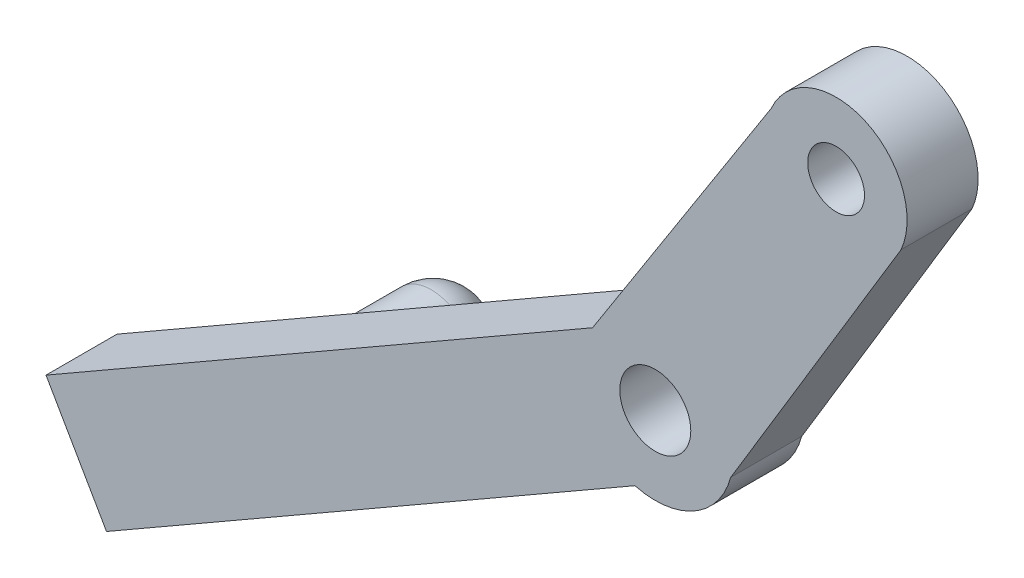
SolidWorks part; units mm, degrees
ref_plane "Front Plane" through (0, 0, 0) normal (0, 0, 1) x (1, 0, 0)
ref_plane "Top Plane" through (0, 0, 0) normal (0, 1, 0) x (1, 0, 0)
ref_plane "Right Plane" through (0, 0, 0) normal (1, 0, 0) x (0, 0, -1)
sketch "Sketch1" plane through (0, 0, 0) normal (0, 0, 1) x (0.4985, -0.8669, 0)
  line L0 (4.6263, -46.838) -> (4.6263, -41.838) construction
  line L2 (8.8991, 3.8691) -> (-2.3564, 24.18)
  line L3 (1.121, -3.909) -> (-10.421, 18.2671)
  line L4 (-2.3564, 24.18) -> (-10.421, 18.2671) construction
  line L6 (0.3536, -46.838) -> (8.8991, -46.838)
  line L7 (0.3536, -46.838) -> (0.3536, -2.4346)
  line L9 (8.8991, -46.838) -> (8.8991, -3.909)
  circle A0 centre (5.01, -0.02) radius 2.5
  arc A1 (1.121, -3.909) -> (8.8991, 3.8691) centre (5.01, -0.02) ccw
  arc A2 (-2.3564, 24.18) -> (-10.421, 18.2671) centre (-6.3887, 21.2235) ccw
  circle A3 centre (-6.3887, 21.2235) radius 2
  circle A5 centre (5.01, -0.02) radius 5.5 construction
  point P16 (10.01, -0.02)
  dimension "D2" = 4
  dimension "D3" = 5
  dimension "D5" = 5
  dimension "D4" = 25
  dimension "D6" = 42.929
  dimension "D7" = 8.5456
  dimension "D8" = 10
  dimension "D1" = 3
extrude "Boss-Extrude1" add sketch "Sketch1" along normal blind 5 contours L2 A2 L3 A1 A3 A0 | A1 L3 L7 L6 L9 region at (8.7385, 5.6702, 0) region at (-20.1011, -16.8788, 0)
sketch "Sketch8" plane through (0, 0, 0) normal (0, 0, -1) x (-1, 0, 0)
  line L0 (38.2963, -27.3606) -> (25.2932, -19.8826) construction
  line L1 (23.2692, -23.6476) -> (36.1662, -31.0645) construction
  line L2 (25.3993, -19.9436) -> (23.2692, -23.6476) construction
  line L3 (38.2963, -27.3606) -> (36.1662, -31.0645) construction
  circle A0 centre (25.2932, -19.8826) radius 3
  dimension "D1" = 6
  dimension "D3" = 4.2728
  dimension "D2" = 15
  dimension "D4" = 14.8776
extrude "Boss-Extrude3" add sketch "Sketch8" along normal blind 10
ref_plane "Plane1" through (2.3064, -4.0104, 0) normal (0.4985, -0.8669, 0) x (-0.8669, -0.4985, 0)
sketch "Sketch9" plane through (2.3064, -4.0104, 0) normal (0.4985, -0.8669, 0) x (-0.8669, -0.4985, 0)
  line L0 (31.838, 10) -> (31.838, 7) construction
  line L1 (34.838, 10) -> (28.838, 10) construction
  line L2 (31.838, 7) -> (34.838, 7) construction
  line L3 (31.838, 10) -> (32.838, 10) construction
  line L4 (32.838, 10) -> (34.838, 10)
  line L5 (34.838, 10) -> (34.838, 7)
  line L6 (34.838, 7.6139) -> (31.838, 7.6139) construction
  arc A0 (34.838, 7) -> (32.838, 10) centre (31.588, 7) ccw
  dimension "D3" = 3
  dimension "D1" = 2
  dimension "D2" = 3
revolve "Cut-Revolve1" cut sketch "Sketch9" angle 360 about L0
sketch "Sketch3" plane through (0, 0, 0) normal (0, 0, -1) x (-1, 0, 0)
  line L0 (36.092, -21.164) -> (18.7546, -11.1934) construction
  line L1 (36.1662, -31.0645) -> (40.4264, -23.6566) construction
  line L2 (40.4264, -23.6566) -> (18.7546, -11.1934) construction
  line L3 (40.4264, -23.6566) -> (1.9342, -1.5202) construction
  line L4 (18.7546, -11.1934) -> (14.4943, -18.6013) construction
  line L5 (36.1662, -31.0645) -> (-1.0478, -9.6632) construction
  line L6 (14.4943, -18.6013) -> (36.1662, -31.0645) construction
  line L7 (36.1662, -31.0645) -> (40.4264, -23.6566)
  line L8 (36.1662, -31.0645) -> (31.8318, -28.5719)
  line L9 (40.4264, -23.6566) -> (36.092, -21.164)
  line L10 (31.8318, -28.5719) -> (36.092, -21.164)
  line L11 (14.4943, -18.6013) -> (18.7546, -11.1934)
  line L12 (14.4943, -18.6013) -> (10.16, -16.1087)
  line L13 (18.7546, -11.1934) -> (14.4202, -8.7007)
  line L14 (10.16, -16.1087) -> (14.4202, -8.7007)
  dimension "D1" = 20
  dimension "D2" = 5
  dimension "D3" = 5
